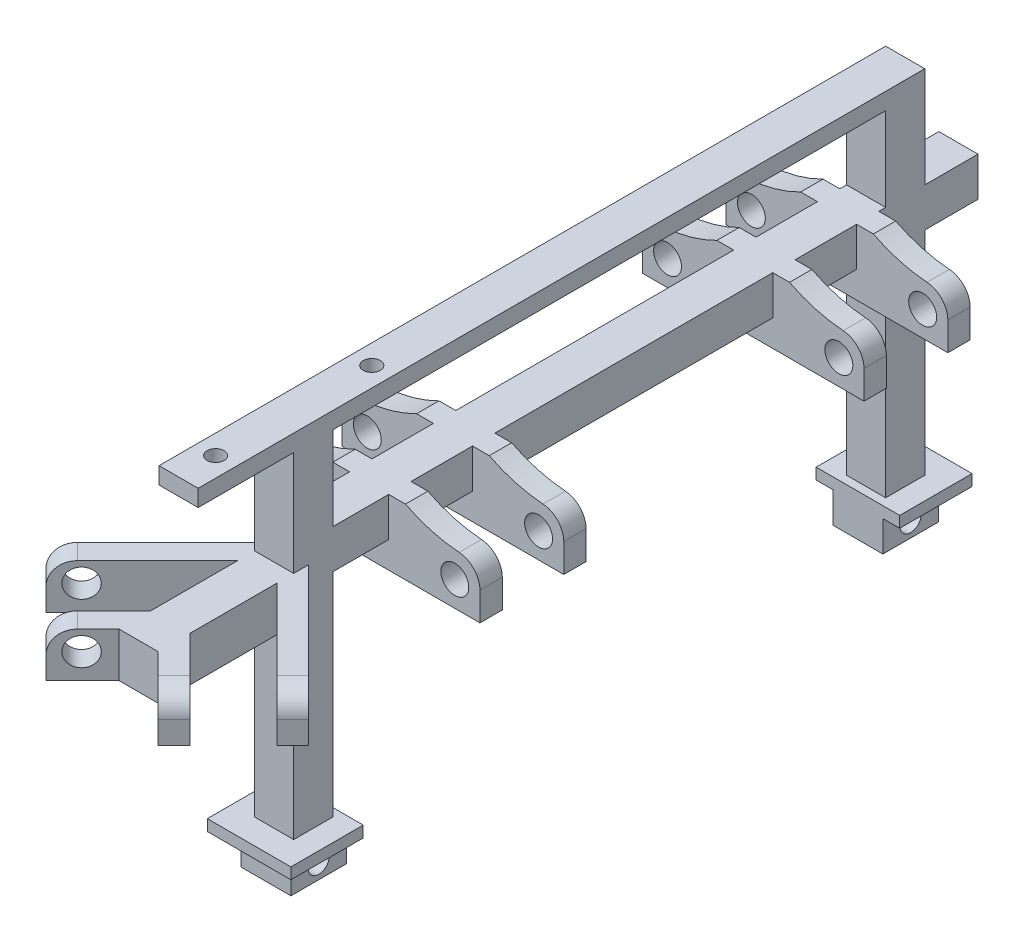
SolidWorks part; units mm, degrees
ref_plane "Front Plane" through (0, 0, 0) normal (0, 0, 1) x (1, 0, 0)
ref_plane "Top Plane" through (0, 0, 0) normal (0, 1, 0) x (1, 0, 0)
ref_plane "Right Plane" through (0, 0, 0) normal (1, 0, 0) x (0, 0, -1)
sketch "Sketch1" plane through (0, 0, 0) normal (0, 1, 0) x (1, 0, 0)
  line L0 (0, 0) -> (0, -105.94) construction
  line L1 (4.47, 4.97) -> (-4.47, 4.97)
  line L2 (4.47, 4.97) -> (4.47, -4.97)
  line L3 (4.47, -4.97) -> (-4.47, -4.97)
  line L4 (-4.47, 4.97) -> (-4.47, -4.97)
  line L5 (4.47, 4.97) -> (-4.47, -4.97) construction
  line L6 (4.47, -4.97) -> (-4.47, 4.97) construction
  line L7 (0, -52.97) -> (25.1393, -52.97) construction
  line L8 (4.47, -100.97) -> (-4.47, -110.91) construction
  line L9 (4.47, -110.91) -> (-4.47, -100.97) construction
  line L10 (-4.47, -110.91) -> (-4.47, -100.97)
  line L11 (4.47, -100.97) -> (-4.47, -100.97)
  line L12 (4.47, -110.91) -> (4.47, -100.97)
  line L13 (4.47, -110.91) -> (-4.47, -110.91)
  point P0 (0, 0)
  dimension "D1" = 8.94
  dimension "D2" = 9.94
  dimension "D3" = 96
extrude "Boss-Extrude1" add sketch "Sketch1" along normal blind 5.5
sketch "Sketch2" plane through (4.47, 0, 0) normal (1, 0, 0) x (0, 0, -1)
  line L0 (0, 5.5) -> (0, 0) construction
  line L1 (-4.97, 5.5) -> (4.97, 5.5) construction
  line L2 (-4.97, 0) -> (4.97, 0) construction
  line L3 (-4.97, 2.75) -> (-100.97, 2.75) construction
  line L4 (-4.97, 5.5) -> (-4.97, 0) construction
  line L5 (-100.97, 5.5) -> (-100.97, 0) construction
  line L6 (-52.97, 2.75) -> (-52.97, 16.4651) construction
  line L7 (-105.94, 5.5) -> (-105.94, 0) construction
  circle A0 centre (0, 2.75) radius 1.9
  circle A1 centre (-105.94, 2.75) radius 1.9
  dimension "D1" = 3.8
extrude "Cut-Extrude1" cut sketch "Sketch2" against normal through all
sketch "Sketch3" plane through (0, 5.5, 0) normal (0, 1, 0) x (1, 0, 0)
  line L0 (-4.47, -4.97) -> (4.47, -4.97) construction
  line L1 (-7.475, -4.97) -> (7.475, -4.97)
  line L2 (-7.475, -4.97) -> (-7.475, 7.98)
  line L3 (-7.475, 7.98) -> (7.475, 7.98)
  line L4 (7.475, -4.97) -> (7.475, 7.98)
  line L5 (0, 4.97) -> (0, -4.97) construction
  line L6 (4.47, 4.97) -> (-4.47, 4.97) construction
  line L7 (0, -4.97) -> (0, -100.97) construction
  line L8 (4.47, -100.97) -> (-4.47, -100.97) construction
  line L9 (0, -52.97) -> (18.6105, -52.97) construction
  line L10 (0, -110.91) -> (0, -100.97) construction
  line L11 (7.475, -100.97) -> (7.475, -113.92)
  line L12 (-7.475, -113.92) -> (7.475, -113.92)
  line L13 (-7.475, -100.97) -> (-7.475, -113.92)
  line L14 (-7.475, -100.97) -> (7.475, -100.97)
  dimension "D1" = 14.95
  dimension "D2" = 12.95
extrude "Boss-Extrude2" add sketch "Sketch3" along normal blind 2
sketch "Sketch4" plane through (0, 7.5, 0) normal (0, 1, 0) x (1, 0, 0)
  line L0 (0, -4.97) -> (0, 7.98) construction
  line L1 (-3.5, -3.5) -> (3.5, -3.5)
  line L2 (-3.5, -3.5) -> (-3.5, 3.5)
  line L3 (-3.5, 3.5) -> (3.5, 3.5)
  line L4 (3.5, -3.5) -> (3.5, 3.5)
  line L5 (-7.475, -4.97) -> (7.475, -4.97) construction
  line L6 (7.475, 7.98) -> (-7.475, 7.98) construction
  line L7 (4.47, 0) -> (-4.47, 0) construction
  line L10 (4.47, -4.97) -> (4.47, 4.97) construction
  line L11 (-4.47, 4.97) -> (-4.47, -4.97) construction
  line L12 (0, -100.97) -> (0, -4.97) construction
  line L13 (7.475, -100.97) -> (-7.475, -100.97) construction
  line L14 (0, -52.97) -> (20.2461, -52.97) construction
  line L15 (4.47, -105.94) -> (-4.47, -105.94) construction
  line L16 (0, -100.97) -> (0, -113.92) construction
  line L17 (3.5, -102.44) -> (3.5, -109.44)
  line L18 (-3.5, -109.44) -> (3.5, -109.44)
  line L19 (-3.5, -102.44) -> (-3.5, -109.44)
  line L20 (-3.5, -102.44) -> (3.5, -102.44)
  dimension "D1" = 7
  dimension "D2" = 7
extrude "Boss-Extrude3" add sketch "Sketch4" along normal blind 45
sketch "Sketch5" plane through (0, 0, 3.5) normal (0, 0, 1) x (1, 0, 0)
  line L0 (3.5, 52.5) -> (3.5, 7.5) construction
  line L1 (-3.5, 52.5) -> (3.5, 52.5)
  line L2 (-3.5, 52.5) -> (-3.5, 45.5)
  line L3 (-3.5, 45.5) -> (3.5, 45.5)
  line L4 (3.5, 52.5) -> (3.5, 45.5)
  dimension "D1" = 7
extrude "Boss-Extrude4" add sketch "Sketch5" along normal up to surface (98.94 mm away) up to face at (0, 30, 102.44)
ref_plane "shell mount 1" through (0, 0, 88.44) normal (0, 0, 1) x (1, 0, 0)
sketch "Sketch6" plane through (0, 0, 88.44) normal (0, 0, 1) x (1, 0, 0)
  line L0 (-15.33, 45.25) -> (-12.83, 45.25) construction
  line L1 (0, 52.5) -> (0, 27.0578) construction
  line L2 (-19.83, 40.75) -> (-19.83, 49.75)
  line L3 (-19.83, 40.75) -> (-3.5, 40.75)
  line L4 (-3.5, 52.5) -> (3.5, 52.5)
  line L5 (-3.5, 52.5) -> (3.5, 52.5) construction
  line L6 (19.83, 40.75) -> (3.5, 40.75)
  line L7 (-3.5, 52.5) -> (-3.5, 7.5) construction
  line L8 (19.83, 40.75) -> (19.83, 49.75)
  line L9 (-3.5, 40.75) -> (3.5, 40.75)
  line L10 (3.5, 52.5) -> (3.5, 7.5) construction
  line L11 (19.83, 49.75) -> (17.899, 49.75)
  line L12 (6.5, 52.5) -> (3.5, 52.5)
  line L13 (-3.5, 52.5) -> (-6.5, 52.5)
  line L14 (-17.899, 49.75) -> (-19.83, 49.75)
  circle A0 centre (-15.33, 45.25) radius 2.5
  circle A1 centre (15.33, 45.25) radius 2.5
  arc A2 (17.899, 49.75) -> (6.5, 52.5) centre (17.899, 74.75) cw
  arc A3 (-17.899, 49.75) -> (-6.5, 52.5) centre (-17.899, 74.75) ccw
  dimension "D1" = 5
  dimension "D5" = 2
  dimension "D2" = 2
  dimension "D7" = 34
  dimension "D3" = 7.25
  dimension "D4" = 11.83
  dimension "D6" = 9
  dimension "D8" = 3
extrude "Boss-Extrude5" add sketch "Sketch6" against normal blind 4 from offset 11 offset against normal yes
extrude "Boss-Extrude6" add sketch "Sketch6<2>" along normal blind 4
sketch "Sketch6<2>" plane through (0, 0, 88.44) normal (0, 0, 1) x (1, 0, 0) same geometry as "Sketch6"
sketch "Sketch7" plane through (0, 0, -3.5) normal (0, 0, -1) x (-1, 0, 0)
  line L0 (3.5, 52.5) -> (3.5, 7.5) construction
  line L1 (-3.5, 52.5) -> (3.5, 52.5)
  line L2 (-3.5, 52.5) -> (-3.5, 45.5)
  line L3 (-3.5, 45.5) -> (3.5, 45.5)
  line L4 (3.5, 52.5) -> (3.5, 45.5)
  line L5 (3.5, 45.5) -> (-3.5, 45.5) construction
extrude "Boss-Extrude7" add sketch "Sketch7" along normal blind 9.52
ref_plane "shell mount 2" through (0, 0, 19.71) normal (0, 0, 1) x (1, 0, 0)
sketch "Sketch9" plane through (0, 0, 19.71) normal (0, 0, 1) x (1, 0, 0)
  line L0 (-3.5, 52.5) -> (3.5, 52.5)
  line L6 (-3.5, 45.5) -> (-3.5, 52.5)
  line L7 (3.5, 45.5) -> (-3.5, 45.5)
  line L8 (3.5, 52.5) -> (3.5, 45.5)
  line L9 (19.83, 40.75) -> (19.83, 49.75)
  line L10 (-19.83, 40.75) -> (19.83, 40.75)
  line L11 (-19.83, 49.75) -> (-19.83, 40.75)
  line L15 (19.83, 40.75) -> (19.83, 49.75)
  line L16 (-19.83, 40.75) -> (19.83, 40.75)
  line L17 (-19.83, 49.75) -> (-19.83, 40.75)
  line L20 (6.5, 52.5) -> (3.5, 52.5)
  line L21 (6.5, 52.5) -> (3.5, 52.5)
  line L22 (19.83, 49.75) -> (17.899, 49.75)
  line L23 (19.83, 49.75) -> (17.899, 49.75)
  line L24 (-17.899, 49.75) -> (-19.83, 49.75)
  line L25 (-17.899, 49.75) -> (-19.83, 49.75)
  line L26 (-3.5, 52.5) -> (-6.5, 52.5)
  line L27 (-3.5, 52.5) -> (-6.5, 52.5)
  circle A0 centre (-15.33, 45.25) radius 2.5 construction
  circle A1 centre (15.33, 45.25) radius 2.5 construction
  circle A2 centre (-15.33, 45.25) radius 2.5
  circle A3 centre (15.33, 45.25) radius 2.5
  arc A6 (6.5, 52.5) -> (17.899, 49.75) centre (17.899, 74.75) ccw
  arc A7 (6.5, 52.5) -> (17.899, 49.75) centre (17.899, 74.75) ccw
  arc A8 (-17.899, 49.75) -> (-6.5, 52.5) centre (-17.899, 74.75) ccw
  arc A9 (-17.899, 49.75) -> (-6.5, 52.5) centre (-17.899, 74.75) ccw
  dimension "D1" = 0
extrude "Boss-Extrude8" add sketch "Sketch9" against normal blind 4 from offset 11 offset against normal yes
extrude "Boss-Extrude9" add sketch "Sketch9<2>" along normal blind 4
sketch "Sketch9<2>" plane through (0, 0, 19.71) normal (0, 0, 1) x (1, 0, 0) same geometry as "Sketch9"
sketch "Sketch10" plane through (0, 40.75, 0) normal (0, -1, 0) x (1, 0, 0)
  line L0 (0, 109.44) -> (0, 112.3502) construction
  line L1 (-3.5, 109.44) -> (3.5, 109.44) construction
  line L2 (0, 116.7511) -> (10.3945, 127.1455) construction
  line L3 (20.6475, 129.6204) -> (3.5, 112.4729)
  line L4 (12.8693, 137.3986) -> (3.5, 128.0292)
  line L5 (20.6475, 129.6204) -> (23.4759, 126.792)
  line L6 (23.4759, 126.792) -> (3.5, 106.816)
  line L7 (12.8693, 137.3986) -> (10.0409, 140.227)
  line L8 (10.0409, 140.227) -> (3.5, 133.6861)
  line L9 (-3.5, 92.44) -> (-3.5, 109.44) construction
  line L10 (-3.5, 109.44) -> (3.5, 109.44)
  line L11 (-3.5, 112.4729) -> (-3.5, 128.0292)
  line L12 (-3.5, 133.6861) -> (3.5, 133.6861)
  line L13 (3.5, 112.4729) -> (3.5, 128.0292)
  line L14 (3.5, 109.44) -> (3.5, 92.44) construction
  line L15 (3.5, 123.61) -> (13.93, 123.61) construction
  line L16 (13.93, 123.61) -> (6.8589, 130.6811) construction
  line L17 (19.5869, 129.2669) -> (12.5158, 136.3379) construction
  line L18 (6.8589, 130.6811) -> (12.5158, 136.3379) construction
  line L19 (13.93, 123.61) -> (19.5869, 129.2669) construction
  line L20 (3.5, 109.44) -> (3.5, 106.816)
  line L21 (-20.6475, 129.6204) -> (-23.4759, 126.792)
  line L22 (-12.8693, 137.3986) -> (-10.0409, 140.227)
  line L23 (-10.0409, 140.227) -> (-3.5, 133.6861)
  line L24 (-12.8693, 137.3986) -> (-3.5, 128.0292)
  line L25 (-3.5, 109.44) -> (-3.5, 106.816)
  line L26 (-20.6475, 129.6204) -> (-3.5, 112.4729)
  line L27 (-23.4759, 126.792) -> (-3.5, 106.816)
  dimension "D1" = 11
  dimension "D2" = 45
  dimension "D3" = 4
  dimension "D4" = 14.17
  dimension "D5" = 10
  dimension "D6" = 10.43
  dimension "D7" = 8
  dimension "D8" = 1
extrude "Boss-Extrude10" add sketch "Sketch10" against normal blind 8
sketch "Sketch11" plane through (51.658, 0, 51.658) normal (-0.7071, 0, -0.7071) x (-0.7071, 0, 0.7071)
  line L0 (73.3765, 45.25) -> (100.7497, 45.25) construction
  line L2 (106.2555, 48.75) -> (106.2555, 40.75) construction
  circle A0 centre (101.7555, 45.25) radius 2.5
  ellipse E0 centre (73.3765, 45.25) end of major axis (73.3765, 42.75) minor radius 1.7678 construction
  ellipse E1 centre (73.3765, 45.25) end of major axis (73.3765, 42.75) minor radius 1.7678 construction
  dimension "D1" = 5
  dimension "D2" = 2
extrude "Cut-Extrude2" cut sketch "Sketch11" against normal through all
sketch "Sketch12" plane through (-51.658, 0, 51.658) normal (0.7071, 0, -0.7071) x (-0.7071, 0, -0.7071)
  line L0 (-73.3765, 45.25) -> (-108.7218, 45.25) construction
  line L3 (-106.2555, 48.75) -> (-106.2555, 40.75) construction
  circle A0 centre (-101.7555, 45.25) radius 2.5
  ellipse E0 centre (-73.3765, 45.25) end of major axis (-73.3765, 47.75) minor radius 1.7678 construction
  ellipse E1 centre (-73.3765, 45.25) end of major axis (-73.3765, 47.75) minor radius 1.7678 construction
  dimension "D1" = 2
  dimension "D2" = 5
extrude "Cut-Extrude3" cut sketch "Sketch12" against normal through all
fillet "Fillet1" radius 4 12 edges at (22.0617, 48.75, 128.2062) (11.4551, 48.75, 138.8128) (-11.4551, 48.75, 138.8128) (-22.0617, 48.75, 128.2062) (-19.83, 49.75, 21.71) (-19.83, 49.75, 6.71) (19.83, 49.75, 6.71) (19.83, 49.75, 21.71) (19.83, 49.75, 90.44) (19.83, 49.75, 75.44) (-19.83, 49.75, 75.44) (-19.83, 49.75, 90.44)
sketch "Sketch13" plane through (0, 52.5, 0) normal (0, 1, 0) x (1, 0, 0)
  line L0 (-3.5, -92.44) -> (-3.5, -109.44) construction
  line L1 (3.5, -109.44) -> (-3.5, -109.44)
  line L2 (3.5, -109.44) -> (3.5, -102.44)
  line L3 (3.5, -102.44) -> (-3.5, -102.44)
  line L4 (-3.5, -109.44) -> (-3.5, -102.44)
  line L5 (3.5, -102.44) -> (-3.5, -102.44) construction
extrude "Boss-Extrude11" add sketch "Sketch13" along normal blind 15
sketch "Sketch14" plane through (0, 67.5, 0) normal (0, 1, 0) x (1, 0, 0)
  line L0 (0, -102.44) -> (0, -85.34) construction
  line L1 (3.5, -85.34) -> (-3.5, -85.34)
  line L2 (3.5, -85.34) -> (3.5, -126.54)
  line L3 (3.5, -126.54) -> (-3.5, -126.54)
  line L4 (-3.5, -85.34) -> (-3.5, -126.54)
  line L5 (3.5, -102.44) -> (-3.5, -102.44) construction
  line L7 (-3.5, -102.44) -> (-3.5, -109.44) construction
  line L8 (3.5, -105.94) -> (20.0322, -105.94) construction
  line L9 (3.5, -109.44) -> (3.5, -102.44) construction
  circle A0 centre (0, -91.97) radius 1.525
  circle A1 centre (0, -119.91) radius 1.525
  dimension "D2" = 3.05
  dimension "D1" = 41.2
  dimension "D3" = 27.94
extrude "Boss-Extrude12" add sketch "Sketch14" along normal blind 3
sketch "Sketch15" plane through (0, 52.5, 0) normal (0, 1, 0) x (1, 0, 0)
  line L0 (3.5, 3.5) -> (-3.5, 3.5) construction
  line L1 (3.5, -3.5) -> (3.5, 3.5) construction
  line L2 (-3.5, -3.5) -> (3.5, -3.5) construction
  line L3 (-3.5, 3.5) -> (-3.5, -3.5) construction
  line L4 (3.5, 3.5) -> (-3.5, 3.5)
  line L5 (3.5, -3.5) -> (3.5, 3.5)
  line L6 (-3.5, -3.5) -> (3.5, -3.5)
  line L7 (-3.5, 3.5) -> (-3.5, -3.5)
extrude "Boss-Extrude13" add sketch "Sketch15" along normal up to surface (15 mm away) up to face at (0, 67.5, 93.495)
sketch "Sketch16" plane through (0, 67.5, 0) normal (0, 1, 0) x (1, 0, 0)
  line L0 (3.5, 3.5) -> (-3.5, 3.5) construction
  line L1 (-3.5, -85.34) -> (3.5, -85.34)
  line L2 (-3.5, -85.34) -> (-3.5, 3.5)
  line L3 (-3.5, 3.5) -> (3.5, 3.5)
  line L4 (3.5, -85.34) -> (3.5, 3.5)
  line L5 (-3.5, -85.34) -> (-3.5, -126.54) construction
  line L6 (3.5, -126.54) -> (3.5, -85.34) construction
  line L7 (3.5, -85.34) -> (-3.5, -85.34) construction
extrude "Boss-Extrude14" add sketch "Sketch16" along normal up to surface (3 mm away) up to face at (0, 70.5, 93.495)
